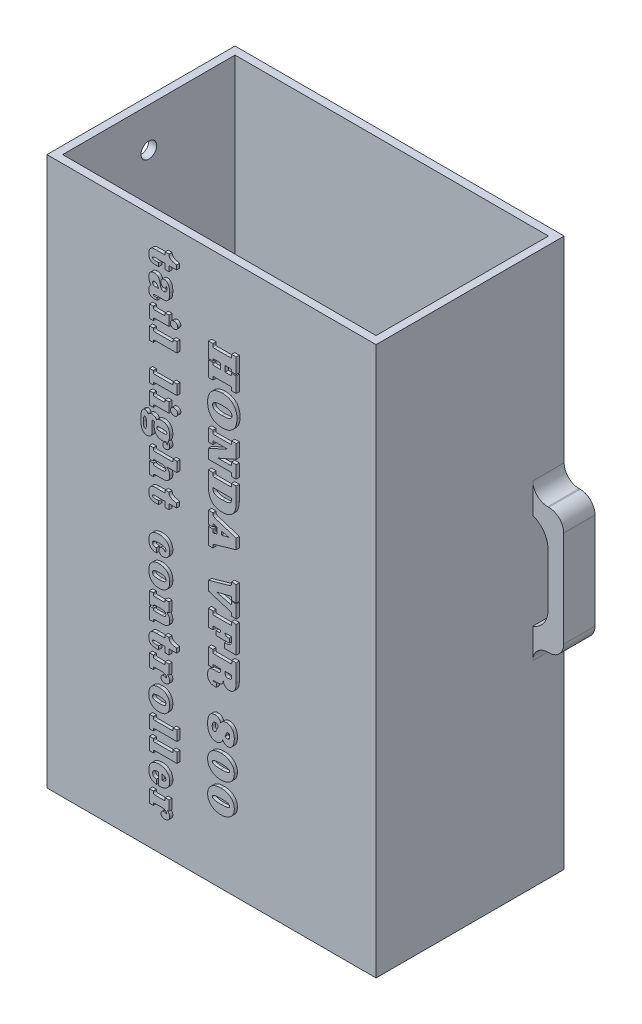
SolidWorks part; units mm, degrees
ref_plane "Front Plane" through (0, 0, 0) normal (0, 0, 1) x (1, 0, 0)
ref_plane "Top Plane" through (0, 0, 0) normal (0, 1, 0) x (1, 0, 0)
ref_plane "Right Plane" through (0, 0, 0) normal (1, 0, 0) x (0, 0, -1)
sketch "Sketch1" plane through (0, 0, 0) normal (0, 1, 0) x (1, 0, 0)
  line L1 (0, 0) -> (42, 0)
  line L2 (0, 0) -> (0, 24)
  line L3 (0, 24) -> (42, 24)
  line L4 (42, 0) -> (42, 24)
extrude "Boss-Extrude1" add sketch "Sketch1" along normal blind 70
shell "Shell1" thickness 1 removed face at (21, 70, -12)
sketch "Sketch2" plane through (0, 0, 0) normal (0, 0, 1) x (1, 0, 0)
  line L0 (21, 70) -> (21, 0) construction
  line L1 (0, 70) -> (42, 70) construction
  line L2 (0, 0) -> (42, 0) construction
  text T0 "<b>HONDA VFR 800</b>\r\ntail light controller" font "Clarendon Blk BT" height 3.5
extrude "Boss-Extrude2" add sketch "Sketch2" along normal blind 0.4
sketch "Sketch4" plane through (0, 0, -24) normal (0, 0, -1) x (-1, 0, 0)
  line L0 (-21, 0) -> (-21, 70) construction
  line L1 (-42, 0) -> (0, 0) construction
  line L2 (-42, 70) -> (0, 70) construction
sketch "Sketch5" plane through (0, 0, -24) normal (0, 0, -1) x (-1, 0, 0)
  line L0 (-42, 70) -> (-42, 0) construction
  line L1 (-45.9413, 43.0347) -> (-41.9413, 43.0347)
  line L2 (-45.9413, 43.0347) -> (-45.9413, 26.9653)
  line L3 (-45.9413, 26.9653) -> (-41.9413, 26.9653)
  line L5 (-45.9413, 43.0347) -> (-42, 35) construction
  line L6 (-45.9413, 26.9653) -> (-42, 35) construction
  line L7 (-41.9413, 43.0347) -> (-41.9413, 41.1202)
  line L8 (-43.9413, 41.1202) -> (-41.9413, 41.1202)
  line L9 (-43.9413, 41.1202) -> (-43.9413, 28.8798)
  line L10 (-43.9413, 28.8798) -> (-41.9413, 28.8798)
  line L12 (-43.9413, 41.1202) -> (-42, 35) construction
  line L13 (-43.9413, 28.8798) -> (-42, 35) construction
  line L14 (-41.9413, 28.8798) -> (-41.9413, 26.9653)
  line L15 (1.9413, 28.8798) -> (-0.0587, 28.8798)
  line L17 (-21, 70) -> (-21, 0)
  line L18 (1.9413, 41.1202) -> (1.9413, 28.8798)
  line L19 (1.9413, 41.1202) -> (-0.0587, 41.1202)
  line L20 (-0.0587, 43.0347) -> (-0.0587, 41.1202)
  line L21 (3.9413, 43.0347) -> (-0.0587, 43.0347)
  line L22 (3.9413, 43.0347) -> (3.9413, 26.9653)
  line L23 (3.9413, 26.9653) -> (-0.0587, 26.9653)
  line L24 (-0.0587, 28.8798) -> (-0.0587, 26.9653)
  point P0 (-42, 35)
  point P7 (-42, 35)
  dimension "D1" = 2
  dimension "D2" = 4
extrude "Boss-Extrude3" add sketch "Sketch5" against normal blind 4 contours L14 L3 L2 L1 L7 L8 L9 L10 | L19 L20 L21 L22 L23 L24 L15 L18
fillet "Fillet1" radius 1.9 8 edges at (0, 43.0347, -22) (-3.9413, 43.0347, -22) (-3.9413, 26.9653, -22) (0, 26.9653, -22) (42, 26.9653, -22) (45.9413, 26.9653, -22) (42, 43.0347, -22) (45.9413, 43.0347, -22)
fillet "Fillet2" radius 2.9 4 edges at (-1.9413, 41.1202, -22) (-1.9413, 28.8798, -22) (43.9413, 28.8798, -22) (43.9413, 41.1202, -22)
sketch "Sketch6" plane through (0, 0, 0) normal (-1, 0, 0) x (0, 0, 1)
  line L0 (-12, 70) -> (-12, 0) construction
  line L1 (-24, 70) -> (0, 70) construction
  line L2 (-24, 0) -> (0, 0) construction
  line L3 (-12, 70) -> (-12, 65)
  circle A0 centre (-12, 65) radius 1
extrude "Cut-Extrude1" cut sketch "Sketch6" against normal up to next contours A0
sketch "Sketch7" plane through (0, 1, 0) normal (0, 1, 0) x (1, 0, 0)
  line L0 (21, 1) -> (21, 23) construction
  line L1 (41, 1) -> (39, 1)
  line L2 (41, 1) -> (41, 6)
  line L3 (41, 6) -> (39, 6)
  line L4 (39, 1) -> (39, 6)
  line L5 (1, 1) -> (41, 1) construction
  line L6 (41, 23) -> (1, 23) construction
  line L7 (1, 6) -> (3, 6)
  line L8 (3, 1) -> (3, 6)
  line L9 (1, 1) -> (3, 1)
  line L10 (1, 1) -> (1, 6)
  dimension "D1" = 2
  dimension "D2" = 5
extrude "Boss-Extrude4" add sketch "Sketch7" along normal blind 61
extrude "Cut-Extrude2" cut sketch "Sketch7<2>" along normal blind 50
sketch "Sketch7<2>" plane through (0, 1, 0) normal (0, 1, 0) x (1, 0, 0) same geometry as "Sketch7"
